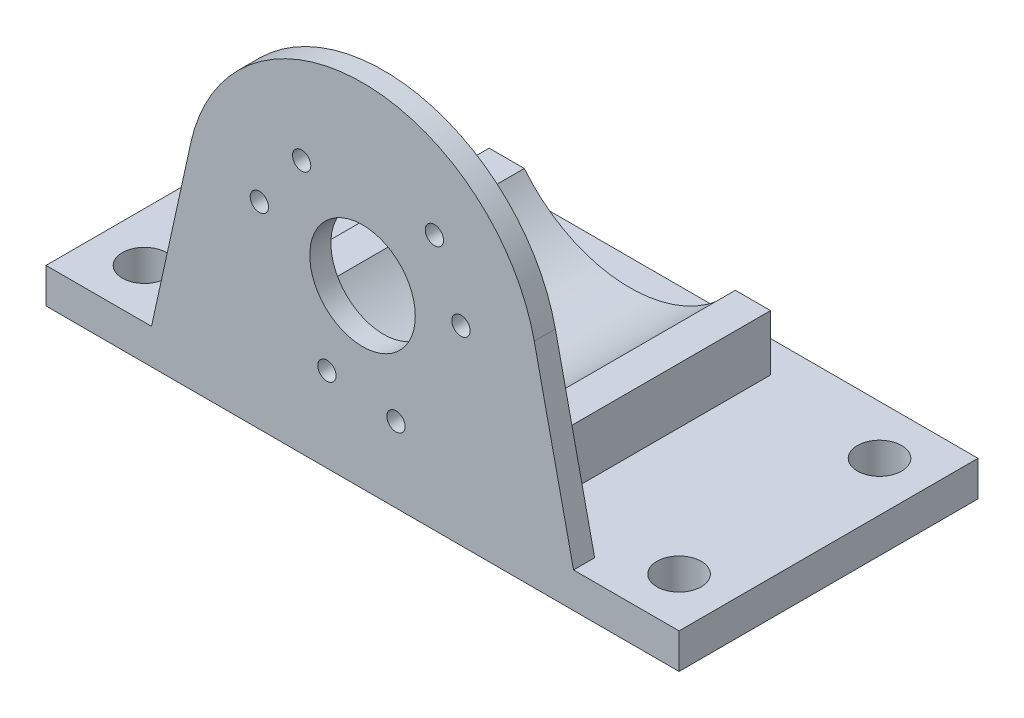
SolidWorks part; units mm, degrees
material "Plain Carbon Steel"
ref_plane "Front Plane" through (0, 0, 0) normal (0, 0, 1) x (1, 0, 0)
ref_plane "Top Plane" through (0, 0, 0) normal (0, 1, 0) x (1, 0, 0)
ref_plane "Right Plane" through (0, 0, 0) normal (1, 0, 0) x (0, 0, -1)
sketch "Sketch3" plane through (0, 0, 0) normal (0, 1, 0) x (1, 0, 0)
  line L0 (-40.6832, 0) -> (52.6999, 0) construction
  line L1 (-45, 21.25) -> (45, 21.25)
  line L2 (-45, 21.25) -> (-45, -21.25)
  line L3 (-45, -21.25) -> (45, -21.25)
  line L4 (45, 21.25) -> (45, -21.25)
  line L5 (0, 26.2262) -> (0, -26.6116) construction
  circle A0 centre (-38, 14.25) radius 3.15
  circle A4 centre (38, 14.25) radius 3.15
  circle A5 centre (38, -14.25) radius 3.15
  circle A6 centre (-38, -14.25) radius 3.15
  point P0 (0, -21.25)
  point P5 (45, 0)
  point P18 (-24.9211, 12.4467)
  dimension "D5" = 6.3
  dimension "D1" = 42.5
  dimension "D2" = 90
  dimension "D3" = 7
  dimension "D4" = 7
extrude "Boss-Extrude1" add sketch "Sketch3" along normal blind 5
sketch "Sketch4" plane through (0, 0, 21.25) normal (0, 0, 1) x (1, 0, 0)
  line L2 (30, 5) -> (24.4157, 30.3735)
  line L3 (-30, 5) -> (-24.4157, 30.3735)
  line L4 (-45, 5) -> (45, 5) construction
  line L6 (-30, 5) -> (30, 5)
  circle A1 centre (0, 25) radius 19
  circle A2 centre (0, 25) radius 3
  circle A3 centre (13.9904, 27.0801) radius 1.3
  circle A4 centre (10.2192, 36.3473) radius 1.3
  circle A5 centre (-8.6549, 36.0875) radius 1.3
  circle A6 centre (-14.6673, 27.9923) radius 1.3
  circle A7 centre (-5.0673, 12.0109) radius 1.3
  circle A8 centre (4.7494, 10.6747) radius 1.3
  circle A9 centre (0, 25) radius 7.5
  arc A10 (24.4157, 30.3735) -> (-24.4157, 30.3735) centre (0, 25) ccw
  point P5 (0, 0)
  point P7 (0, 0)
  point P8 (0, 25)
  point P24 (-23.8996, 32.3356)
  point P27 (0, 0)
  point P28 (-35.7634, 3)
  point P31 (0, 0)
  point P32 (30.813, 3)
  line M7 (45, 5) -> (-45, 5)
  dimension "D1" = 38
  dimension "D2" = 6
  dimension "D3" = 2.6
  dimension "D4" = 13.9904
  dimension "D5" = 2.0801
  dimension "D6" = 4.7494
  dimension "D8" = 12.9891
  dimension "D17" = 15
  dimension "D18" = 50
  dimension "D7" = 14.3253
  dimension "D10" = 2.9923
  dimension "D9" = 5.0673
  dimension "D11" = 14.6673
  dimension "D12" = 8.6549
  dimension "D13" = 11.0875
  dimension "D14" = 11.3473
  dimension "D15" = 10.2192
  dimension "D16" = 25
  dimension "D19" = 15
  dimension "D20" = 15
extrude "Boss-Extrude2" add sketch "Sketch4" against normal blind 3 contours A1 A8 A7 A6 A5 A4 A3 A2 | A1 L3 L2 M7 region at (0, 5.75, 21.25) region at (-18.4626, 25, 21.25)
sketch "Sketch5" plane through (0, 0, 18.25) normal (0, 0, -1) x (-1, 0, 0)
  line L1 (-15, 12.9351) -> (-15, 0)
  line L5 (-45, 0) -> (45, 0) construction
  line L7 (-15, 0) -> (15, 0)
  line L9 (15, 0) -> (15, 12.9351)
  line L11 (-20, 12.9351) -> (20, 12.9351)
  line L12 (-20, 12.9351) -> (-20, 0)
  line L13 (-20, 0) -> (20, 0)
  line L14 (20, 12.9351) -> (20, 0)
  circle A3 centre (0, 25) radius 7.5 construction
  circle A4 centre (0, 25) radius 7.5
  circle A5 centre (0, 25) radius 19.25
  point P14 (0, 0)
  line M36 (-30, 5) -> (30, 5)
  dimension "D2" = 30
  dimension "D1" = 38.5
  dimension "D3" = 5
extrude "Boss-Extrude3" add sketch "Sketch5" along normal blind 35 contours A5 L1 L9 M36 | L11 L12 L1 M36 | L14 L11 L9 M36 region at (0, 5.4397, 18.25) region at (17.5, 8.9675, 18.25) region at (-17.5, 8.9675, 18.25)
